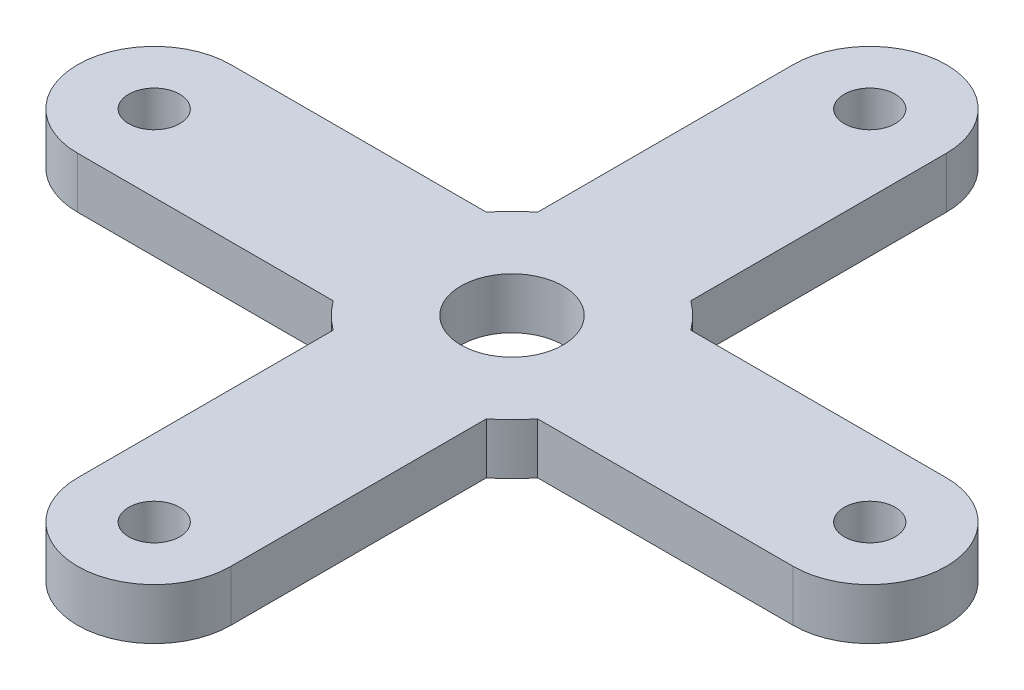
SolidWorks part; units mm, degrees
ref_plane "Front Plane" through (0, 0, 0) normal (0, 0, 1) x (1, 0, 0)
ref_plane "Top Plane" through (0, 0, 0) normal (0, 1, 0) x (1, 0, 0)
ref_plane "Right Plane" through (0, 0, 0) normal (1, 0, 0) x (0, 0, -1)
sketch "Sketch4" plane through (0, 0, 0) normal (0, 1, 0) x (1, 0, 0)
  line L0 (0, 0) -> (7, 0) construction
  line L1 (7, 1.5) -> (2, 1.5) construction
  line L2 (7, -1.5) -> (2, -1.5) construction
  line L3 (7, 1.5) -> (2, 1.5)
  line L4 (2, -1.5) -> (7, -1.5)
  line L5 (1.5, -7) -> (1.5, -2)
  line L6 (-1.5, -2) -> (-1.5, -7)
  line L7 (-7, -1.5) -> (-2, -1.5)
  line L8 (-2, 1.5) -> (-7, 1.5)
  line L9 (-1.5, 7) -> (-1.5, 2)
  line L10 (1.5, 2) -> (1.5, 7)
  circle A0 centre (0, 0) radius 2.5
  circle A1 centre (0, 0) radius 2
  circle A2 centre (7, 0) radius 1.5
  circle A3 centre (7, 0) radius 0.5
  circle A4 centre (0, 0) radius 1
  circle A5 centre (0, -7) radius 1.5
  circle A6 centre (0, -7) radius 0.5
  circle A7 centre (-7, 0) radius 1.5
  circle A8 centre (-7, 0) radius 0.5
  circle A9 centre (0, 7) radius 1.5
  circle A10 centre (0, 7) radius 0.5
  point P36 (0, 0)
  dimension "D1" = 4
extrude "Boss-Extrude1" add sketch "Sketch4" along normal blind 1 contours A9 A10 | A9 L9 A0 L10 | A2 L3 A0 L4 | A2 A3 | A0 A1 | A1 A4 | A7 A8 | A7 L7 A0 L8 | A5 L5 A0 L6 | A5 A6 region at (4.0943, 0, 0) region at (8.0307, 0, -1.0307) region at (2.3046, 0, -0.7682) region at (0, 0, -4.0943) region at (0, 0, -5.5424) region at (0, 0, 4.0943) region at (-4.0943, 0, 0) region at (0, 0, 8.4576) region at (-5.9693, 0, -1.0307) region at (-1.9434, 0, 0)
